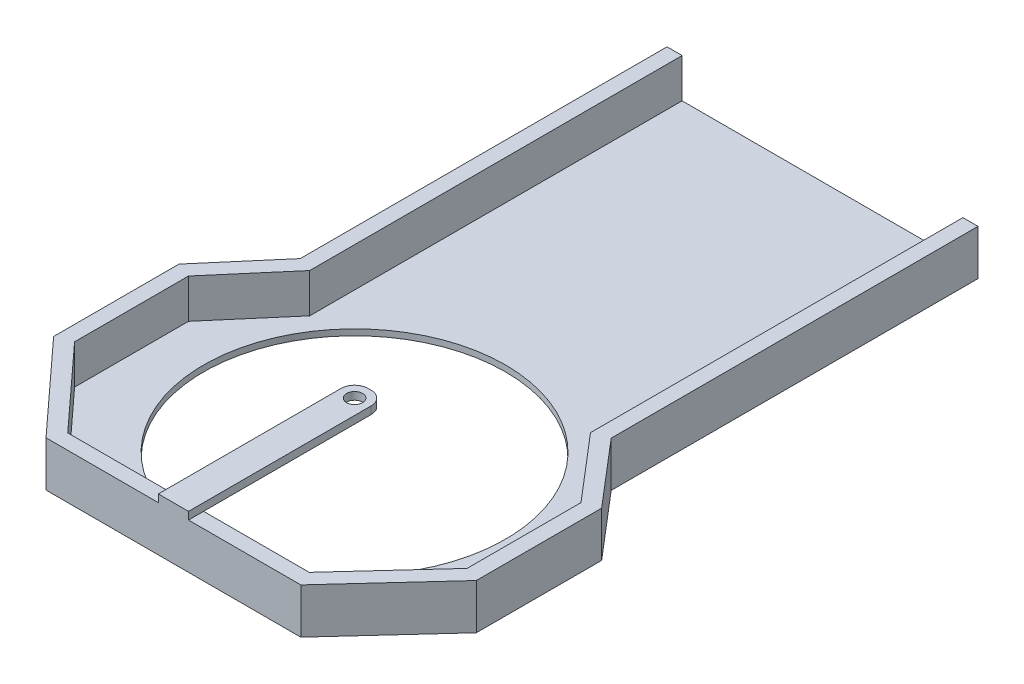
SolidWorks part; units mm, degrees
ref_plane "Front Plane" through (0, 0, 0) normal (0, 0, 1) x (1, 0, 0)
ref_plane "Top Plane" through (0, 0, 0) normal (0, 1, 0) x (1, 0, 0)
ref_plane "Right Plane" through (0, 0, 0) normal (1, 0, 0) x (0, 0, -1)
sketch "Sketch1" plane through (0, 0, 0) normal (0, 1, 0) x (1, 0, 0)
  line L1 (-46.5, 140) -> (46.5, 140)
  line L2 (46.5, 21.654) -> (46.5, 140)
  line L3 (-40, -65) -> (40, -65)
  line L9 (-65, 0) -> (-46.5, 21.654)
  line L10 (-65, 0) -> (-65, -37.7326)
  line L11 (-65, -37.7326) -> (-40, -65)
  line L12 (65, 0) -> (65, -37.7326)
  line L13 (40, -65) -> (65, -37.7326)
  line L14 (65, 0) -> (46.5, 21.654)
  line L15 (-46.5, 21.654) -> (-46.5, 140)
  circle A0 centre (0, -10) radius 50 construction
  point P0 (0, -10)
  point P4 (0, 0)
  point P12 (0, -65)
  point P16 (0, -10)
  dimension "D4" = 55
  dimension "D5" = 80
  dimension "D6" = 130
  dimension "D7" = 130
extrude "Boss-Extrude1" add sketch "Sketch1" along normal blind 2 contours L15 L1 L2 L14 L12 L13 L3 L11 L10 L9
extrude "Extrude-Thin3" add sketch "Sketch1<6>" along normal blind 15 thin thin type one direction wall 5
sketch "Sketch1<6>" plane through (0, 0, 0) normal (0, 1, 0) x (1, 0, 0) same geometry as "Sketch1"
sketch "Sketch3" plane through (0, 0, -140) normal (0, 0, 1) x (1, 0, 0)
  line L0 (46.5, 15) -> (46.5, 2) construction
  line L1 (-46.5, 15) -> (46.5, 15)
  line L2 (-46.5, 15) -> (-46.5, 2)
  line L3 (-46.5, 2) -> (46.5, 2)
  line L4 (46.5, 15) -> (46.5, 2)
  line L5 (-46.5, 2) -> (46.5, 2) construction
extrude "Cut-Extrude1" cut sketch "Sketch3" against normal up to surface (5 mm away) up to face at (0, 7.5, -145)
sketch "Sketch4" plane through (0, 15, 0) normal (0, 1, 0) x (1, 0, 0)
  line L0 (-42.1992, -70) -> (42.1992, -70) construction
  line L1 (-0.5, -5) -> (0.5, -5)
  line L2 (-5, -9.5) -> (-5, -70)
  line L3 (-5, -70) -> (5, -70)
  line L4 (5, -9.5) -> (5, -70)
  line L5 (-5, -5) -> (5, -70) construction
  line L6 (-5, -70) -> (5, -5) construction
  circle A0 centre (0, -10) radius 2.65
  arc A1 (5, -9.5) -> (0.5, -5) centre (0.5, -9.5) ccw
  arc A2 (-0.5, -5) -> (-5, -9.5) centre (-0.5, -9.5) ccw
  point P0 (0, -37.5)
  point P7 (0, -10)
  dimension "D1" = 5.3
  dimension "D2" = 4.5
  dimension "D3" = 65
sketch "Sketch5" plane through (0, 2, 0) normal (0, 1, 0) x (1, 0, 0)
  circle A0 centre (0, -10) radius 50
extrude "Cut-Extrude2" cut sketch "Sketch5" against normal up to surface (2 mm away) up to face at (0, 0, -12.1332)
extrude "Boss-Extrude2" add sketch "Sketch4" along normal blind 2.5 contours L2 L3 L4 A1 L1 A2
extrude "Cut-Extrude3" cut sketch "Sketch4<3>" along normal up to surface (2.5 mm away) contours A0 up to face at (0, 17.5, 27.856)
sketch "Sketch4<3>" plane through (0, 15, 0) normal (0, 1, 0) x (1, 0, 0) same geometry as "Sketch4"
